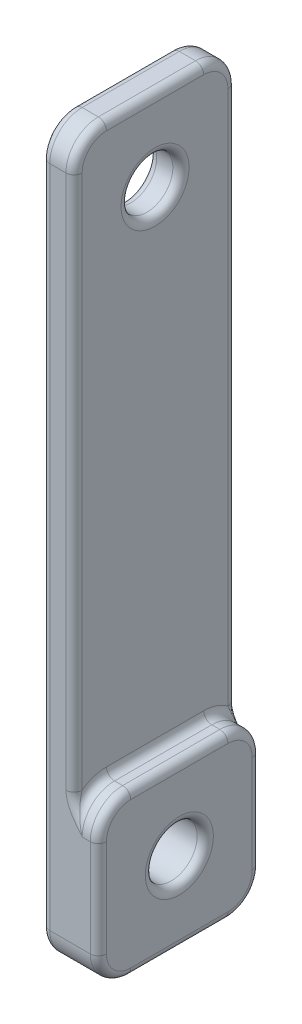
SolidWorks part; units mm, degrees
ref_plane "Спереди" through (0, 0, 0) normal (0, 0, 1) x (1, 0, 0)
ref_plane "Сверху" through (0, 0, 0) normal (0, 1, 0) x (1, 0, 0)
ref_plane "Справа" through (0, 0, 0) normal (1, 0, 0) x (0, 0, -1)
sketch "Эскиз1" plane through (0, 0, 0) normal (0, 0, 1) x (1, 0, 0)
  line L0 (0, 0) -> (0, 45)
  line L1 (0, 45) -> (2, 45)
  line L2 (2, 45) -> (2, 10)
  line L3 (2, 10) -> (3.5, 10)
  line L4 (3.5, 10) -> (3.5, 0)
  line L5 (3.5, 0) -> (0, 0)
  dimension "D1" = 45
  dimension "D2" = 2
  dimension "D3" = 1.5
  dimension "D4" = 10
extrude "Бобышка-Вытянуть2" add sketch "Эскиз1" along normal blind 10
sketch "Эскиз4" plane through (0, 0, 0) normal (-1, 0, 0) x (0, 0, 1)
  line L0 (10, 45) -> (0, 45) construction
  line L1 (5, 46.3755) -> (5, -1.7261) construction
  line L2 (10, 0) -> (0, 0) construction
  circle A0 centre (5, 40) radius 1.6
  circle A1 centre (5, 5) radius 1.6
  point P0 (5, 45)
  dimension "D1" = 3.2
  dimension "D2" = 5
  dimension "D3" = 5
extrude "Вырез-Вытянуть1" cut sketch "Эскиз4" against normal through all
fillet "Скругление1" radius 0.5 4 edges at (0, 5, 6.6) (3.5, 5, 6.6) (2, 38.4, 5) (0, 40, 6.6)
fillet "Скругление2" radius 2 6 edges at (1.75, 0, 0) (1.75, 0, 10) (1, 45, 0) (1, 45, 10) (2.75, 10, 0) (2.75, 10, 10)
fillet "Скругление3" radius 0.5 24 edges at (3.5, 5, 0) (3.5, 0.5858, 0.5858) (3.5, 0, 5) (3.5, 0.5858, 9.4142) (2, 25.5, 0) (2, 44.4142, 0.5858) (2, 45, 5) (2, 44.4142, 9.4142) (0, 44.4142, 9.4142) (0, 45, 5) (0, 44.4142, 0.5858) (0, 22.5, 0) (0, 0.5858, 0.5858) (0, 0, 5) (0, 0.5858, 9.4142) (3.5, 5, 10) (3.5, 10, 5) (2, 25.5, 10) (0, 22.5, 10) (3.5, 9.4142, 9.4142) (3.5, 9.4142, 0.5858) (2, 9.4142, 9.4142) (2, 9.4142, 0.5858) (2, 10, 5)
